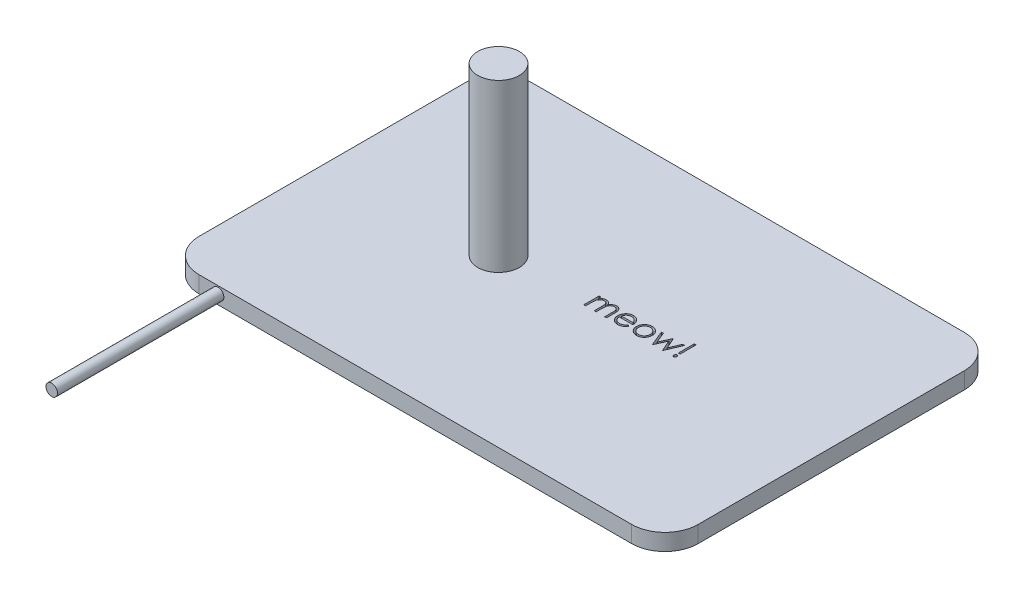
SolidWorks part; units mm, degrees
ref_plane "Front Plane" through (0, 0, 0) normal (0, 0, 1) x (1, 0, 0)
ref_plane "Top Plane" through (0, 0, 0) normal (0, 1, 0) x (1, 0, 0)
ref_plane "Right Plane" through (0, 0, 0) normal (1, 0, 0) x (0, 0, -1)
sketch "Sketch2" plane through (0, 0, 0) normal (0, 1, 0) x (1, 0, 0)
  line L1 (38.1, 25.4) -> (-38.1, 25.4)
  line L2 (38.1, 25.4) -> (38.1, -25.4)
  line L3 (38.1, -25.4) -> (-38.1, -25.4)
  line L4 (-38.1, 25.4) -> (-38.1, -25.4)
  line L6 (-38.1, 25.4) -> (38.1, -25.4) construction
  line L7 (-38.1, -25.4) -> (38.1, 25.4) construction
  point P4 (0, 0)
  dimension "D1" = 76.2
  dimension "D2" = 50.8
extrude "Boss-Extrude1" add sketch "Sketch2" along normal blind 2.54 contours L4 L3 L2 L1
fillet "Fillet1" radius 5.08 4 edges at (38.1, 1.27, -25.4) (38.1, 1.27, 25.4) (-38.1, 1.27, -25.4) (-38.1, 1.27, 25.4)
sketch "Sketch3" plane through (0, 2.54, 0) normal (0, 1, 0) x (1, 0, 0)
  line L0 (-1.397, 0) -> (1.397, 0) construction
  line L1 (-38.1, 20.32) -> (-38.1, -20.32) construction
  circle A0 centre (-12.7, 0) radius 3.175
  dimension "D2" = 6.35
  dimension "D1" = 25.4
extrude "Boss-Extrude2" add sketch "Sketch3" along normal blind 25.4
sketch "Sketch5" plane through (0, 2.54, 0) normal (0, 1, 0) x (1, 0, 0)
  text T0 "meow!"
extrude "Cut-Extrude1" cut sketch "Sketch5" against normal through all
sketch "Sketch6" plane through (0, 0, 25.4) normal (0, 0, 1) x (1, 0, 0)
  circle A0 centre (-30.1241, 1.4595) radius 0.8815
extrude "Boss-Extrude3" add sketch "Sketch6" along normal blind 25.4
